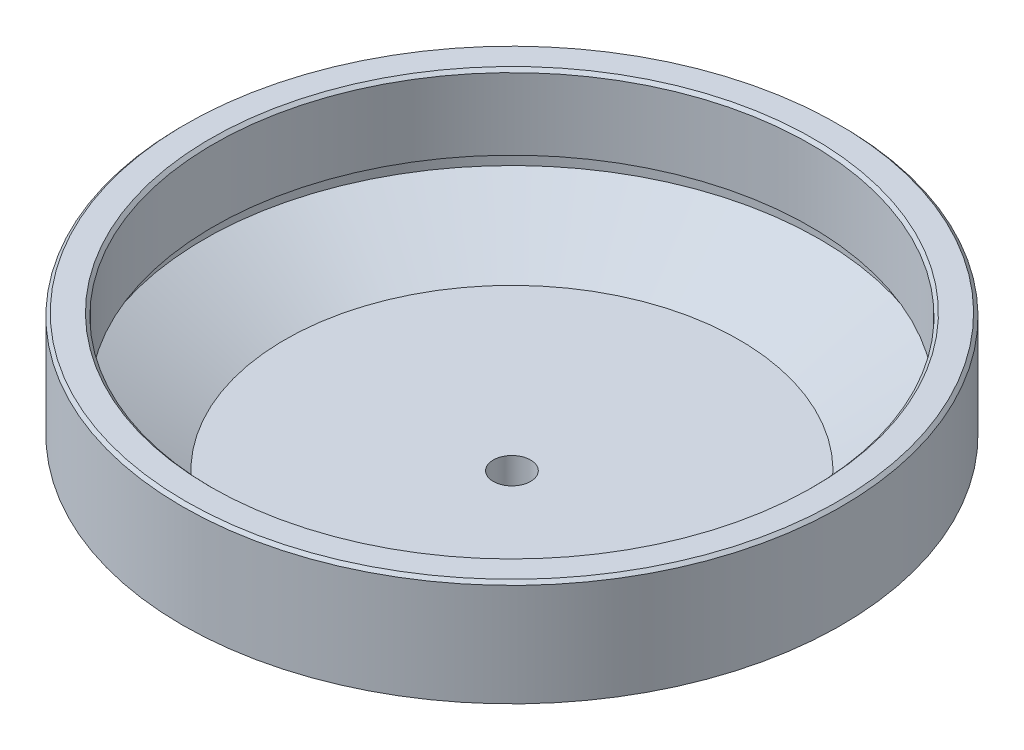
SolidWorks part; units mm, degrees
material "AISI 304"
ref_plane "Спереди" through (0, 0, 0) normal (0, 0, 1) x (1, 0, 0)
ref_plane "Сверху" through (0, 0, 0) normal (0, 1, 0) x (1, 0, 0)
ref_plane "Справа" through (0, 0, 0) normal (1, 0, 0) x (0, 0, -1)
ref_axis "ОсьX" through (-88.99, 0, 0) along (1, 0, 0)
ref_axis "ОсьZ" through (0, 55, 0) along (0, -1, 0)
ref_axis "ОсьY" through (0, 0, -88.99) along (0, 0, 1)
sketch "Эскиз1" plane through (0, 0, 0) normal (0, 0, 1) x (1, 0, 0)
  line L0 (-53, 28) -> (-53, 11)
  line L1 (0, 26.169) -> (0, -22.1581) construction
  line L2 (-33.9474, 0) -> (-3, 0)
  line L3 (-3, 0) -> (-3, 6)
  line L4 (-3, 6) -> (-36.5096, 6)
  line L5 (-49.5, 13.5) -> (-49.5, 16)
  line L6 (-49.5, 16) -> (-48, 16)
  line L7 (-48, 16) -> (-48, 28)
  line L8 (-48, 28) -> (-53, 28)
  line L11 (-53, 11) -> (-33.9474, 0)
  line L12 (-49.5, 13.5) -> (-36.5096, 6)
  dimension "D1" = 106
  dimension "D2" = 60
  dimension "D3" = 96
  dimension "D4" = 6
  dimension "D5" = 6
  dimension "D6" = 17
  dimension "D7" = 1.5
  dimension "D8" = 2.5
  dimension "D9" = 12
  dimension "D10" = 28
revolve "Повернуть1" add sketch "Эскиз1" angle 360 mid plane about L1
cosmetic thread "Условное изображение резьбы1" parameters "D2"=100
cosmetic thread "Условное изображение резьбы2" parameters "D2"=8
chamfer "Фаска1" distance 0.5 angle 45 3 edges at (0, 0, 3) (0, 28, 53) (0, 28, 48)
